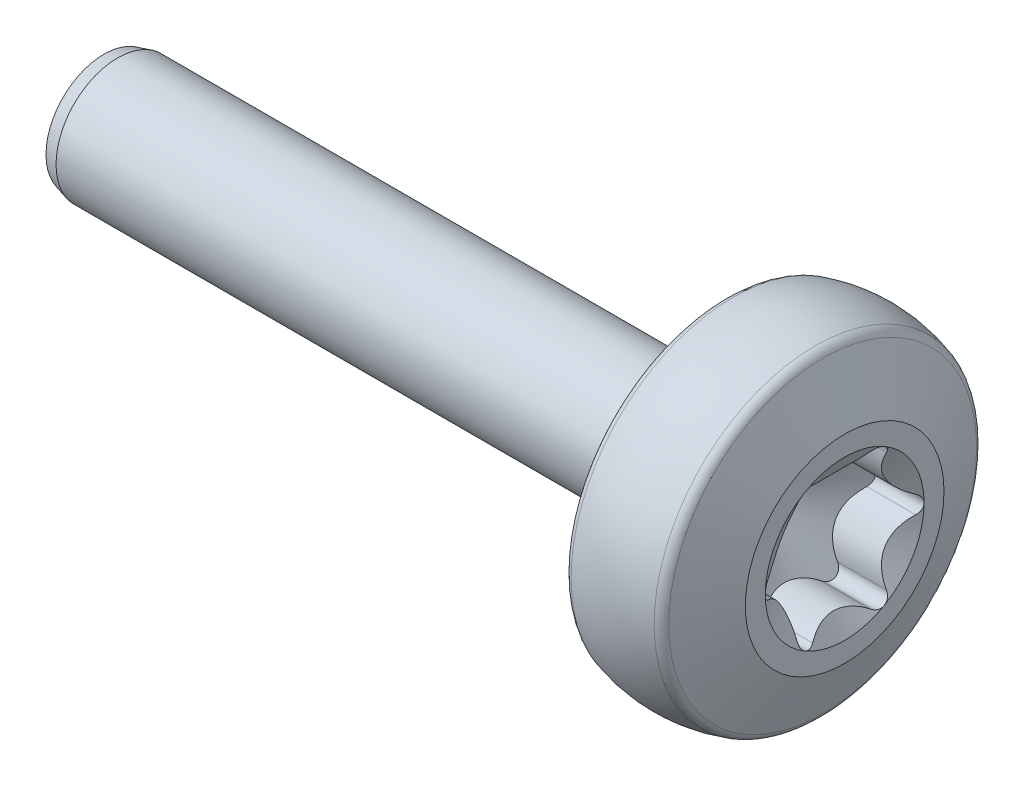
SolidWorks part; units mm, degrees
material "Alloy Steel"
ref_plane "Front Plane" through (0, 0, 0) normal (0, 0, 1) x (1, 0, 0)
ref_plane "Top Plane" through (0, 0, 0) normal (0, 1, 0) x (1, 0, 0)
ref_plane "Right Plane" through (0, 0, 0) normal (1, 0, 0) x (0, 0, -1)
sketch "Sketch1" plane through (0, 0, 0) normal (0, 0, 1) x (1, 0, 0)
  line L0 (-7.5819, 0) -> (7.5819, 0) construction
  line L1 (-7.5819, 1.8669) -> (-7.5819, -1.8669) construction
  line L2 (5.1181, 3.429) -> (5.1181, -3.429) construction
  line L3 (7.5819, 1.6256) -> (7.5819, -1.6256) construction
  line L4 (-8.0147, 2.0116) -> (-7.4298, 0.9986) construction
  line L5 (-7.4298, 0.9986) -> (-8.5996, 0.9986) construction
  line L6 (-8.5996, 0.9986) -> (-8.0147, 2.0116) construction
  line L7 (-8.5996, 0.9986) -> (-8.6831, 0.8539) construction
  line L8 (-8.6831, 0.8539) -> (-7.3463, 0.8539) construction
  line L9 (-7.3463, 0.8539) -> (-7.4298, 0.9986) construction
  line L10 (-8.0983, 1.8669) -> (-7.9312, 1.8669) construction
  line L11 (-8.0147, 2.0116) -> (-8.0147, 1.8669) construction
  line L12 (-8.0147, 0.9986) -> (-8.0147, 0.8539) construction
  point P11 (5.1181, 0)
  point P12 (-7.5819, 1.262)
  dimension "Screw Size Decimal Equivalent" = 3.7338
  dimension "Torx Diameter" = 3.2512
  dimension "Head Diameter" = 6.858
  dimension "Head Height" = 2.4638
  dimension "Length" = 12.7
  dimension "Thread ID" = 2.524
  dimension "Approximate Thread Pitch" = 1.3368
  dimension "D1" = 0.1671
sketch "Sketch2" plane through (0, 0, 0) normal (0, 0, 1) x (1, 0, 0)
  line L0 (-7.5819, 0) -> (7.5819, 0)
  line L1 (7.5819, 0) -> (7.5819, 2.0336)
  line L2 (-7.5819, 0) -> (-7.5819, 1.262)
  line L3 (-7.5819, 1.262) -> (5.0419, 1.262)
  line L6 (5.0419, 1.262) -> (5.0419, 1.9272)
  line L9 (-7.5819, 0) -> (-22.7457, 0) construction
  line L10 (5.0419, 1.9272) -> (5.0419, 2.5924) construction
  line L11 (7.5819, 1.6256) -> (7.5819, 2.0336) construction
  line L12 (5.0419, 2.5924) -> (5.0419, 3.2576) construction
  line L14 (7.5819, 3.2576) -> (5.1181, 3.2576) construction
  line L15 (5.1181, 3.2576) -> (5.1181, 1.262) construction
  line L17 (5.1181, 3.2576) -> (5.1181, 2.0034)
  line L18 (5.1181, 3.429) -> (5.1181, -3.429) construction
  line L19 (7.5819, 1.6256) -> (7.5819, -1.6256) construction
  line L20 (7.5819, 2.0336) -> (7.5819, 2.4416) construction
  line L21 (7.5819, 2.4416) -> (7.5819, 2.8496) construction
  line L22 (7.5819, 2.8496) -> (7.5819, 3.2576) construction
  line L23 (7.5819, 2.0336) -> (7.0891, 3.2576)
  arc A6 (7.0891, 3.2576) -> (5.1181, 3.2576) centre (6.1036, 0.5108) ccw
  arc A7 (5.1181, 2.0034) -> (5.08, 1.9653) centre (5.08, 2.0034) cw
  arc A8 (5.08, 1.9653) -> (5.0419, 1.9272) centre (5.08, 1.9272) ccw
  point P14 (6.1036, 3.429)
  dimension "D1" = 6.5151
  dimension "D2" = 0.0762
  dimension "D3" = 1.971
revolve "Revolve1" add sketch "Sketch2" angle 360 about L9
sketch "Sketch12" plane through (0, 0, 0) normal (0, 0, 1) x (1, 0, 0)
  line L0 (7.5819, 1.6256) -> (6.581, 1.6256)
  line L1 (6.581, 1.6256) -> (5.6424, 0)
  line L2 (-7.5819, 0) -> (7.5819, 0) construction
  line L3 (5.6424, 0) -> (7.5819, 0)
  line L4 (7.5819, 0) -> (7.5819, 1.6256)
  dimension "D1" = 60
  dimension "D2" = 1.0009
revolve "Cut-Revolve3" cut sketch "Sketch12" angle 360 about L0
sketch "Sketch3" plane through (7.5819, 0, 0) normal (1, 0, 0) x (0, 0, -1)
  line L0 (1.2192, 0) -> (1.4224, 0) construction
  line L1 (1.4224, 0) -> (1.6256, 0) construction
  line L2 (-0.8128, 1.4078) -> (0, 0) construction
  line L3 (0, 0) -> (0.8128, 1.4078) construction
  line L4 (0.8128, 1.4078) -> (-0.8128, 1.4078) construction
  circle A0 centre (0, 0) radius 1.6256 construction
  circle A1 centre (0, 0) radius 1.4224 construction
  circle A2 centre (0, 0) radius 1.2192 construction
  circle A51 centre (0, 0) radius 2.0336
  arc A54 (1.5122, -0.1823) -> (1.6256, 0) centre (1.4224, 0) ccw
  arc A55 (-0.5983, 1.4008) -> (0.5983, 1.4008) centre (0, 2.2957) ccw
  arc A56 (-0.5983, 1.4008) -> (-0.8128, 1.4078) centre (-0.7112, 1.2318) ccw
  arc A57 (1.5122, -0.1823) -> (0.914, -1.2185) centre (1.9881, -1.1478) ccw
  arc A58 (0.8128, 1.4078) -> (0.5983, 1.4008) centre (0.7112, 1.2318) ccw
  arc A59 (0.914, 1.2185) -> (0.8128, 1.4078) centre (0.7112, 1.2318) ccw
  arc A60 (0.8128, -1.4078) -> (0.914, -1.2185) centre (0.7112, -1.2318) ccw
  arc A61 (0.914, 1.2185) -> (1.5122, 0.1823) centre (1.9881, 1.1478) ccw
  arc A62 (1.6256, 0) -> (1.5122, 0.1823) centre (1.4224, 0) ccw
  arc A63 (0.5983, -1.4008) -> (0.8128, -1.4078) centre (0.7112, -1.2318) ccw
  arc A76 (0.5983, -1.4008) -> (-0.5983, -1.4008) centre (0, -2.2957) ccw
  arc A77 (-0.8128, -1.4078) -> (-0.5983, -1.4008) centre (-0.7112, -1.2318) ccw
  arc A78 (-0.914, -1.2185) -> (-0.8128, -1.4078) centre (-0.7112, -1.2318) ccw
  arc A79 (-0.914, -1.2185) -> (-1.5122, -0.1823) centre (-1.9881, -1.1478) ccw
  arc A80 (-1.6256, 0) -> (-1.5122, -0.1823) centre (-1.4224, 0) ccw
  arc A81 (-1.5122, 0.1823) -> (-1.6256, 0) centre (-1.4224, 0) ccw
  arc A82 (-1.5122, 0.1823) -> (-0.914, 1.2185) centre (-1.9881, 1.1478) ccw
  arc A83 (-0.8128, 1.4078) -> (-0.914, 1.2185) centre (-0.7112, 1.2318) ccw
  point P20 (0, 1.2192)
  point P58 (0, 0)
  point P72 (0, 0)
  dimension "D1" = 2.4384
  dimension "D2" = 6
extrude "Boss-Extrude1" add sketch "Sketch3" against normal up to surface (1.0601 mm away)
sketch "Sketch4" plane through (7.5819, 0, 0) normal (1, 0, 0) x (0, 0, -1)
  circle A0 centre (0, 0) radius 1.6256
extrude "Cut-Extrude2" cut sketch "Sketch4" against normal through all draft 60
fillet "Fillet1" radius 0.2464 2 edges at (5.1181, 0, -3.2576) (7.0891, 0, -3.2576)
chamfer "Chamfer1" distance 0.2807 angle 15 1 edges at (-7.5819, 0, -1.262) first distance on face at (-7.5819, 0, -1.262)
split "Split1" [suppressed] bodies to split 106
sketch "Sketch9" [suppressed] plane through (0, 0, 0) normal (0, 0, 1) x (1, 0, 0)
  line L0 (-7.5819, 1.8669) -> (-7.5819, 0)
  line L1 (-7.5819, 0) -> (5.0419, 0)
  line L2 (-7.5819, 0) -> (7.5819, 0) construction
  line L3 (5.0419, 0) -> (5.0419, 1.8669)
  line L5 (5.0419, 1.8669) -> (-7.5819, 1.8669)
revolve "Revolve2" [suppressed] add sketch "Sketch9" angle 360 about L0
sketch "Sketch5" [suppressed] plane through (-7.5819, 0, 0) normal (-1, 0, 0) x (0, 0, 1)
  circle A0 centre (0, 0) radius 1.262
curve "Helix/Spiral1" [suppressed] pitch 1.3368 height 15.3737 turns 11.5
sketch "Sketch7" [suppressed] plane through (0, 0, 0) normal (0, 0, 1) x (1, 0, 0)
  line L0 (-7.5819, 1.262) -> (-7.8135, 1.324) construction
  line L1 (-7.8135, 1.324) -> (-7.959, 1.8669) construction
  line L2 (-8.0983, 1.8669) -> (-7.9312, 1.8669) construction
  line L3 (-7.959, 1.8669) -> (-8.0704, 1.8669) construction
  line L4 (-8.0704, 1.8669) -> (-8.2159, 1.324)
  line L5 (-8.2159, 1.324) -> (-8.4475, 1.262)
  line L6 (-8.5996, 0.9986) -> (-8.0147, 2.0116) construction
  line L7 (-8.4475, 1.262) -> (-8.4475, 0.9986) construction
  line L8 (-7.4298, 0.9986) -> (-8.5996, 0.9986) construction
  line L9 (-8.4475, 0.9986) -> (-7.5819, 0.9986) construction
  line L10 (-7.5819, 0.9986) -> (-7.5819, 1.262) construction
  line L11 (-8.0147, 0.9986) -> (-8.0147, 0.8539) construction
  line L12 (-8.6831, 0.8539) -> (-8.7667, 0.9986) construction
  line L13 (-8.7667, 0.9986) -> (-9.3515, 2.0116) construction
  line L14 (-8.0147, 2.0116) -> (-7.4298, 0.9986) construction
  line L15 (-7.3463, 0.8539) -> (-7.4298, 0.9986) construction
  line L16 (-8.9187, 1.262) -> (-8.4475, 1.262)
  line L19 (-8.9187, 1.262) -> (-9.1504, 1.324)
  line L20 (-9.1504, 1.324) -> (-9.2958, 1.8669)
  line L22 (-9.2958, 1.8669) -> (-9.2958, 2.0116)
  line L23 (-9.2958, 2.0116) -> (-8.0704, 2.0116)
  line L24 (-8.0704, 2.0116) -> (-8.0704, 1.8669)
  point P33 (-4.6169, -1.8669)
  dimension "D3" = 0.1114
  dimension "D1" = 15
  dimension "D2" = 15
  dimension "D4" = 3.3421
sweep "Cut-Sweep1" [suppressed] cut profiles "Sketch7" path "Helix/Spiral1"
combine bodies "Combine1" [suppressed] operation type add bodies to combine 107 113 119
sketch "Sketch13" [suppressed] plane through (5.0419, 0, 0) normal (-1, 0, 0) x (0, 0, 1)
  circle A0 centre (0, 0) radius 1.8415
  point P3 (0, 1.8415)
  dimension "D1" = 0.0254
extrude "Boss-Extrude2" [suppressed] add sketch "Sketch13" along normal through all draft 45
sketch "Sketch14" [suppressed] plane through (-7.5819, 0, 0) normal (-1, 0, 0) x (0, 0, 1)
  circle A2 centre (0, 0) radius 1.2366
  point P1 (0, 1.2366)
  dimension "D1" = 0.0254
extrude "Cut-Extrude3" [suppressed] cut sketch "Sketch14" against normal up to next draft 45 flip side to cut draft outward yes
equation "\"Thread ID@Sketch1\"=\"Screw Size Decimal Equivalent@Sketch1\"-(\"Approximate Thread Pitch@Sketch1\"*.905)"
equation "\"D1@Sketch3\"=\"Torx Diameter@Sketch1\"*.75"
equation "\"D4@Helix/Spiral1\"=\"Approximate Thread Pitch@Sketch1\""
equation "\"D3@Helix/Spiral1\"=\"Length@Sketch1\"+2*\"Approximate Thread Pitch@Sketch1\""
equation "\"D1@Sketch1\"=\"Approximate Thread Pitch@Sketch1\"/8"
equation "\"D3@Sketch7\"=\"Approximate Thread Pitch@Sketch1\"/12"
equation "\"D4@Sketch7\"=\"Approximate Thread Pitch@Sketch1\"*2.5"
equation "\"D2@Sketch12\"= \"Head Height@Sketch1\" * .40625"
equation "\"D1@Sketch2\"=\"Head Diameter@Sketch1\"*.95"
equation "\"D3@Sketch2\"=\"Head Height@Sketch1\"*.8"
equation "\"D1@Fillet1\"=\"Head Height@Sketch1\" * .1"
equation "\"D1@Chamfer1\"=\"approximate thread pitch@sketch1\"*.21"
